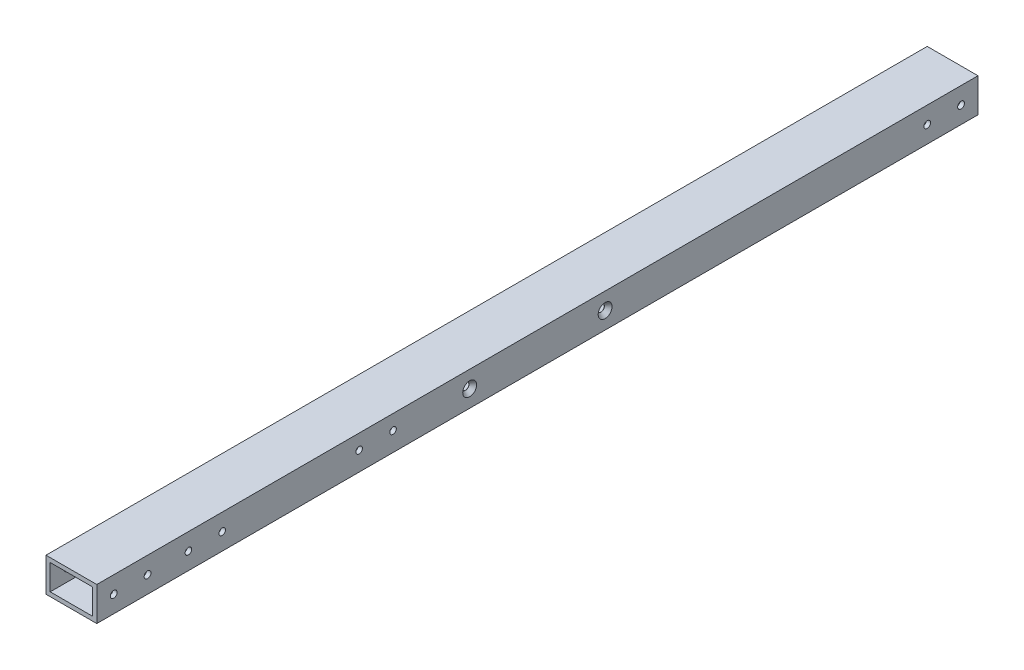
SolidWorks part; units mm, degrees
ref_plane "Front Plane" through (0, 0, 0) normal (0, 0, 1) x (1, 0, 0)
ref_plane "Top Plane" through (0, 0, 0) normal (0, 1, 0) x (1, 0, 0)
ref_plane "Right Plane" through (0, 0, 0) normal (1, 0, 0) x (0, 0, -1)
sketch "Sketch1" plane through (0, 0, 0) normal (0, 0, 1) x (1, 0, 0)
  line L0 (-15.875, 9.525) -> (15.875, 9.525)
  line L2 (-19.05, 12.7) -> (19.05, 12.7)
  line L3 (-19.05, 12.7) -> (-19.05, -12.7)
  line L4 (-19.05, -12.7) -> (19.05, -12.7)
  line L5 (19.05, 12.7) -> (19.05, -12.7)
  line L10 (15.875, 9.525) -> (15.875, -9.525)
  line L11 (-15.875, -9.525) -> (15.875, -9.525)
  line L12 (-15.875, 9.525) -> (-15.875, -9.525)
  point P12 (0, 12.7)
  point P14 (19.05, 0)
  dimension "Wall Thickness" = 3.175
  dimension "Outside Width" = 38.1
  dimension "Outside Height" = 25.4
  dimension "Inside Height" = 19.05
  dimension "Inside Width" = 31.75
sketch "Sketch2" plane through (0, 0, 0) normal (1, 0, 0) x (0, 0, -1)
  line L0 (330.5556, 0) -> (-330.5556, 0)
  point P4 (0, 0)
  point P7 (-330.5556, 0)
  point P10 (330.5556, 0)
  dimension "Length" = 661.1112
sketch "Sketch3" plane through (0, 0, 0) normal (0, 0, 1) x (1, 0, 0)
  line L21 (19.05, 12.7) -> (-19.05, 12.7)
  line L22 (19.05, -12.7) -> (19.05, 12.7)
  line L23 (-19.05, -12.7) -> (19.05, -12.7)
  line L24 (-19.05, 12.7) -> (-19.05, -12.7)
  line L25 (19.05, 12.7) -> (-19.05, 12.7)
  line L26 (19.05, -12.7) -> (19.05, 12.7)
  line L27 (-19.05, -12.7) -> (19.05, -12.7)
  line L28 (-19.05, 12.7) -> (-19.05, -12.7)
  line L29 (15.875, 9.525) -> (-15.875, 9.525)
  line L30 (15.875, -9.525) -> (15.875, 9.525)
  line L31 (-15.875, -9.525) -> (15.875, -9.525)
  line L32 (-15.875, 9.525) -> (-15.875, -9.525)
  line L33 (15.875, 9.525) -> (-15.875, 9.525)
  line L34 (15.875, -9.525) -> (15.875, 9.525)
  line L35 (-15.875, -9.525) -> (15.875, -9.525)
  line L36 (-15.875, 9.525) -> (-15.875, -9.525)
  dimension "D1" = 0
  dimension "D2" = 0
extrude "Boss-Extrude1" add sketch "Sketch3" along normal up to vertex (330.5556 mm away) and the other way up to vertex (330.5556 mm away) up to point (0, 0, 330.5556) other way up to point (0, 0, -330.5556)
sketch "Drawing Reference" plane through (0, 0, 0) normal (1, 0, 0) x (0, 0, -1)
  line L0 (-330.5556, 0) -> (330.5556, 0) construction
  line L1 (0, -12.7) -> (0, 12.7) construction
  line L2 (-330.5556, -12.7) -> (330.5556, -12.7) construction
  line L5 (-330.5556, 12.7) -> (330.5556, 12.7) construction
  point P7 (-303.1236, 0)
  point P8 (303.1236, 0)
  dimension "D1" = 27.432
sketch "Sketch4" plane through (-19.05, 0, 0) normal (-1, 0, 0) x (0, 0, 1)
  line L0 (-330.5556, 0) -> (-317.8556, 0)
  line L1 (-330.5556, 12.7) -> (-330.5556, -12.7) construction
  line L2 (-317.8556, 0) -> (-292.4556, 0)
  line L3 (330.5556, 12.7) -> (330.5556, -12.7) construction
  line L4 (330.5556, 0) -> (317.8556, 0)
  line L5 (317.8556, 0) -> (292.4556, 0)
  line L6 (0, 0) -> (50.8, 0) construction
  line L7 (0, 0) -> (-50.8, 0) construction
  point P11 (-317.8556, 0)
  point P13 (-292.4556, 0)
  point P14 (317.8556, 0)
  point P15 (292.4556, 0)
hole_wizard "#10 Clearance Hole2" positions "Sketch11" profile "Sketch12" hole size "#10" standard "ANSI Inch" end condition through all
sketch "Sketch11" plane through (-19.05, 0, 0) normal (-1, 0, 0) x (0, 0, 1)
  point P0 (-317.8556, 0)
  point P3 (-292.4556, 0)
  point P6 (292.4556, 0)
  point P9 (317.8556, 0)
sketch "Sketch12" plane through (-19.05, 0, -317.8556) normal (0, 1, 0) x (0, 0, 1)
  line L0 (0, 0) -> (0, 38.1)
  line L1 (0, 38.1) -> (2.5527, 38.1)
  line L2 (2.5527, 38.1) -> (2.5527, 0)
  line L5 (2.5527, 0) -> (0, 0)
  line L11 (0, -6.35) -> (0, 107.95) construction
  dimension "Thru Hole Dia." = 5.1054
  dimension "Thru Hole Depth" = 38.1
hole_wizard "#10 (0.1935) Diameter Hole1" positions "Sketch14" profile "Sketch16" hole size "#10" standard "ANSI Inch" end condition through all
sketch "Sketch14" plane through (19.05, 0, 0) normal (1, 0, 0) x (0, 0, -1)
  point P17 (-261.8407, 0)
  point P20 (-236.4407, 0)
  point P25 (-133.6967, 1.5875)
  point P28 (-108.2967, 1.5875)
sketch "Sketch16" plane through (19.05, 0, 261.8407) normal (0, 1, 0) x (0, 0, -1)
  line L0 (0, 0) -> (0, 38.1)
  line L1 (0, 38.1) -> (2.4574, 38.1)
  line L2 (2.4574, 38.1) -> (2.4574, 0)
  line L5 (2.4574, 0) -> (0, 0)
  line L11 (0, -6.35) -> (0, 107.95) construction
  dimension "Thru Hole Dia." = 4.9149
  dimension "Thru Hole Depth" = 38.1
sketch "Sketch17" plane through (19.05, 0, 0) normal (1, 0, 0) x (0, 0, -1)
  point P0 (-261.8407, 0)
  point P1 (-236.4407, 0)
hole_wizard "#10 (0.1935) Diameter Hole2" positions "Sketch18" profile "Sketch19" hole size "#10" standard "ANSI Inch" end condition through all
sketch "Sketch18" plane through (19.05, 0, 0) normal (1, 0, 0) x (0, 0, -1)
  point P0 (-261.8407, 0)
  point P3 (-236.4407, 0)
sketch "Sketch19" plane through (19.05, 0, 261.8407) normal (0, 1, 0) x (0, 0, -1)
  line L0 (0, 0) -> (0, 38.1)
  line L1 (0, 38.1) -> (2.4574, 38.1)
  line L2 (2.4574, 38.1) -> (2.4574, 0)
  line L5 (2.4574, 0) -> (0, 0)
  line L11 (0, -6.35) -> (0, 107.95) construction
  dimension "Thru Hole Dia." = 4.9149
  dimension "Thru Hole Depth" = 38.1
hole_wizard "#10 Clearance Hole3" positions "Sketch20" profile "Sketch21" hole size "#10" standard "ANSI Inch" end condition through all
sketch "Sketch20" plane through (-19.05, 0, 0) normal (-1, 0, 0) x (0, 0, 1)
  point P0 (-50.8, 0)
  point P3 (50.8, 0)
sketch "Sketch21" plane through (-19.05, 0, -50.8) normal (0, 1, 0) x (0, 0, 1)
  line L0 (0, 0) -> (0, 38.1)
  line L1 (0, 38.1) -> (5.207, 38.1)
  line L2 (2.5527, 35.0466) -> (2.5527, 0)
  line L5 (2.5527, 0) -> (0, 0)
  line L7 (5.207, 38.1) -> (2.5527, 35.0466)
  line L8 (-5.207, 38.1) -> (-2.5527, 35.0466) construction
  line L11 (0, -6.35) -> (0, 107.95) construction
  dimension "Thru Hole Dia." = 5.1054
  dimension "Thru Hole Depth" = 38.1
  dimension "Far C'Sink Dia." = 10.414
  dimension "Far C'Sink Angle" = 82
equation "\"D1@Drawing Reference\"=\"Outside Width@Sketch1\" * 0.72"
